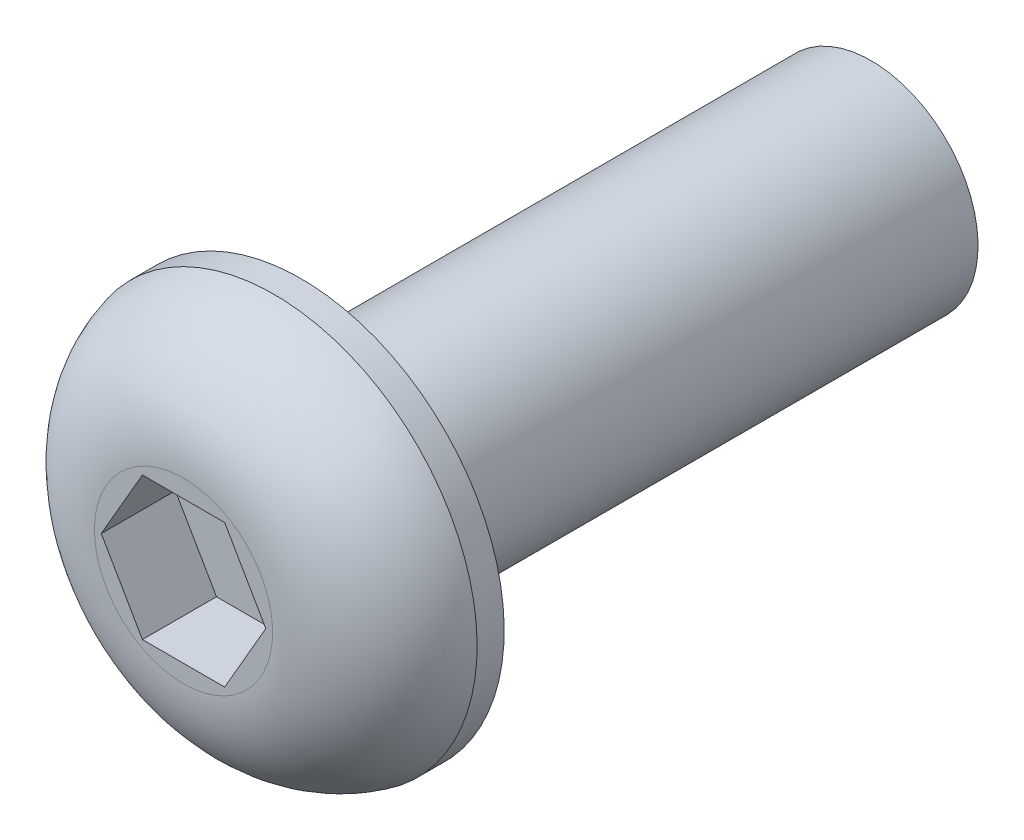
SolidWorks part; units mm, degrees
material "AISI 304"
ref_plane "Front Plane" through (0, 0, 0) normal (0, 0, 1) x (1, 0, 0)
ref_plane "Top Plane" through (0, 0, 0) normal (0, 1, 0) x (1, 0, 0)
ref_plane "Right Plane" through (0, 0, 0) normal (1, 0, 0) x (0, 0, -1)
ref_axis "Axis1" through (0, 0, -52.8182) along (0, 0, 1)
ref_axis "Axis2" through (0, -15.5981, 0) along (0, 1, 0)
ref_axis "Axis3" through (-12.2581, 0, 0) along (1, 0, 0)
sketch "Sketch1" plane through (0, 0, 0) normal (1, 0, 0) x (0, 0, -1)
  line L0 (-1.65, 0) -> (-1.65, 1.25)
  line L1 (-0.38, 2.85) -> (0, 2.85)
  line L2 (0, 2.85) -> (0, 1.5)
  line L3 (0, 1.5) -> (8, 1.5)
  line L4 (8, 1.5) -> (8, 0)
  line L5 (8, 0) -> (-1.65, 0)
  line L6 (-5.5849, 0) -> (13.8966, 0) construction
  arc A0 (-0.38, 2.85) -> (-1.65, 1.25) centre (-0.0071, 1.25) ccw
  dimension "D1" = 3
  dimension "D2" = 5.7
  dimension "D3" = 1.65
  dimension "D4" = 2.5
  dimension "Length" = 8
  dimension "D5" = 0.38
revolve "Revolve1" add sketch "Sketch1" angle 360 about L6
cosmetic thread "Cosmetic Thread1" parameters "D1"=8, "D2"=2.439
sketch "Sketch2" plane through (0, 0, 1.65) normal (0, 0, 1) x (1, 0, 0)
  line L1 (0.5774, -1) -> (1.1547, 0)
  line L2 (1.1547, 0) -> (0.5774, 1)
  line L3 (0.5774, 1) -> (-0.5774, 1)
  line L4 (-0.5774, 1) -> (-1.1547, 0)
  line L5 (-1.1547, 0) -> (-0.5774, -1)
  line L6 (-0.5774, -1) -> (0.5774, -1)
  circle A0 centre (0, 0) radius 1 construction
  dimension "D1" = 2
extrude "Cut-Extrude1" cut sketch "Sketch2" against normal blind 1.04
